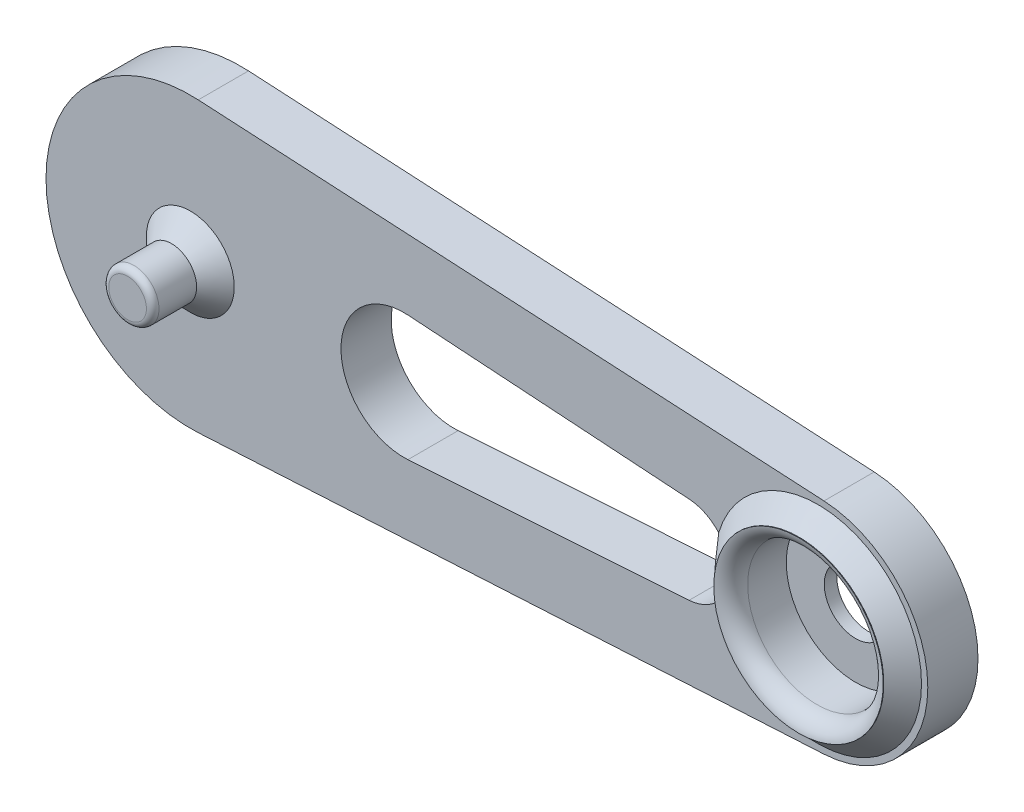
SolidWorks part; units mm, degrees
ref_plane "Front Plane" through (0, 0, 0) normal (1, 0, 0) x (0, 1, 0)
ref_plane "Top Plane" through (0, 0, 0) normal (0, 0, 1) x (0, 1, 0)
ref_plane "Right Plane" through (0, 0, 0) normal (0, 1, 0) x (-1, 0, 0)
sketch "Sketch5" plane through (0, 0, 0) normal (0, 0, 1) x (0, 1, 0)
  circle A0 centre (0, 0) radius 4
  dimension "D1" = 8
extrude "Boss-Extrude1" add sketch "Sketch5" along normal blind 10
sketch "Sketch13" plane through (0, 0, 0) normal (0, 0, 1) x (0, 1, 0)
  line L0 (0, 0) -> (0, -39.3295) construction
  line L1 (-17.4735, -100.9625) -> (-22.9652, -1.265)
  line L2 (17.4735, -100.9625) -> (22.9652, -1.265)
  line L3 (-9.9778, -34.6667) -> (-6.9844, -79.4667)
  line L4 (9.9778, -34.6667) -> (6.9844, -79.4667)
  arc A0 (22.9652, -1.265) -> (-22.9652, -1.265) centre (0, 0) ccw
  arc A1 (-17.4735, -100.9625) -> (17.4735, -100.9625) centre (0, -100) ccw
  arc A2 (-6.9844, -79.4667) -> (6.9844, -79.4667) centre (0, -79) ccw
  arc A3 (9.9778, -34.6667) -> (-9.9778, -34.6667) centre (0, -34) ccw
  circle A4 centre (0, -100) radius 5
  dimension "D1" = 46
  dimension "D2" = 35
  dimension "D6" = 10
  dimension "D7" = 7
  dimension "D8" = 10
  dimension "D3" = 100
  dimension "D4" = 34
  dimension "D5" = 45
extrude "Boss-Extrude5" add sketch "Sketch13" against normal blind 8
chamfer "Chamfer1" distance 3 angle 45 1 edges at (4, 0, 0)
fillet "Fillet1" radius 1 1 edges at (4, 0, 10)
sketch "Sketch14" plane through (0, 0, 0) normal (0, 0, 1) x (0, 1, 0)
  circle A0 centre (0, -100) radius 13.5
  dimension "D1" = 27
extrude "Boss-Extrude6" add sketch "Sketch14" along normal blind 3.1 from surface starting at face at (7, 0, 0)
sketch "Sketch15" plane through (0, 0, 0) normal (0, 0, 1) x (0, 1, 0)
  circle A0 centre (0, -100) radius 11.05
  dimension "D1" = 22.1
extrude "Cut-Extrude1" cut sketch "Sketch15" along normal blind 20 from offset 6 offset against normal yes
fillet "Fillet2" radius 3 1 edges at (111.05, 0, 3.1)
chamfer "Chamfer2" distance 3 angle 45 1 edges at (113.5, 0, 0)
